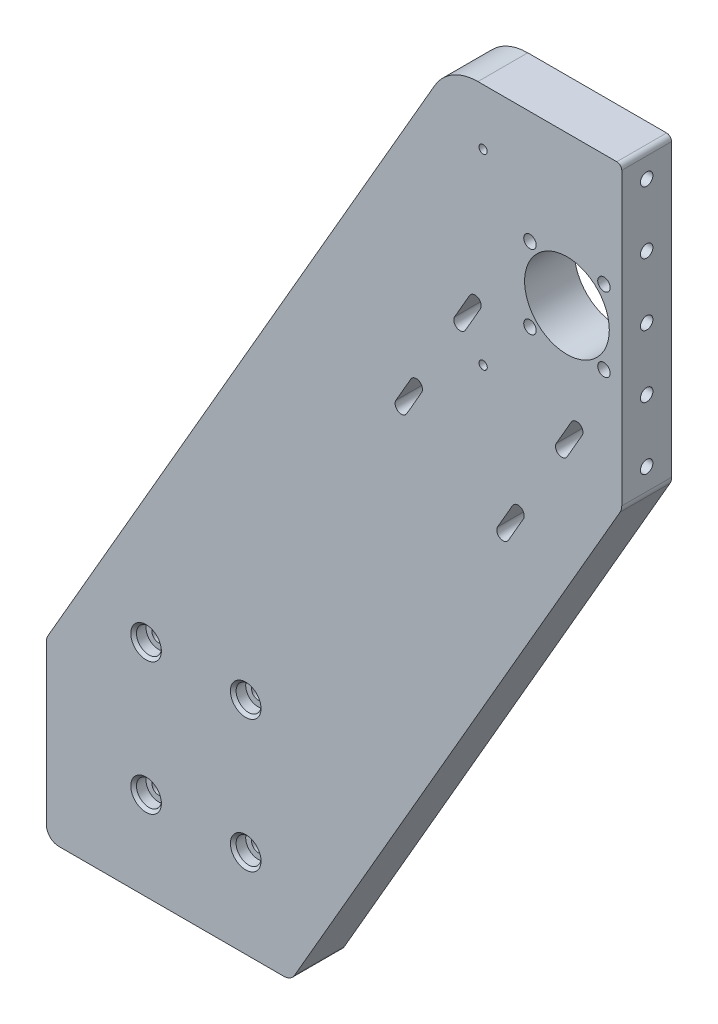
SolidWorks part; units mm, degrees
ref_plane "Piano frontale" through (0, 0, 0) normal (0, 0, 1) x (1, 0, 0)
ref_plane "Piano superiore" through (0, 0, 0) normal (0, 1, 0) x (1, 0, 0)
ref_plane "Piano destro" through (0, 0, 0) normal (1, 0, 0) x (0, 0, -1)
sketch "Schizzo1" plane through (0, 0, 0) normal (0, 0, 1) x (1, 0, 0)
  line L0 (5, 0) -> (95.2628, 0)
  line L1 (99.5929, 2.5) -> (230.2702, 228.8397)
  line L2 (230.9401, 231.3397) -> (230.9401, 348)
  line L3 (228.9401, 350) -> (173.2051, 350)
  line L4 (0, 68.6603) -> (0, 5)
  line L5 (155.8846, 340) -> (0.6699, 71.1603)
  line L9 (208.9401, 290) -> (194.0909, 304.8492) construction
  line L10 (208.9401, 290) -> (187.9401, 290) construction
  line L11 (208.9401, 290) -> (208.9401, 311) construction
  line L12 (50.1314, 0) -> (50.1314, 156.8301) construction
  circle A4 centre (208.9401, 290) radius 17
  circle A5 centre (208.9401, 290) radius 21 construction
  arc A6 (99.5929, 2.5) -> (95.2628, 0) centre (95.2628, 5) cw
  arc A7 (5, 0) -> (0, 5) centre (5, 5) cw
  arc A8 (0, 68.6603) -> (0.6699, 71.1603) centre (5, 68.6603) cw
  arc A9 (230.9401, 231.3397) -> (230.2702, 228.8397) centre (225.9401, 231.3397) cw
  arc A10 (230.9401, 348) -> (228.9401, 350) centre (228.9401, 348) ccw
  arc A11 (173.2051, 350) -> (155.8846, 340) centre (173.2051, 330) ccw
  circle A14 centre (223.7894, 304.8492) radius 2.5
  circle A15 centre (223.7894, 275.1508) radius 2.5
  circle A18 centre (194.0909, 275.1508) radius 2.5
  circle A19 centre (194.0909, 304.8492) radius 2.5
  point P27 (194.0909, 304.8492)
  point P28 (223.7894, 304.8492)
  point P29 (223.7894, 275.1508)
  point P30 (194.0909, 275.1508)
  point P31 (230.9401, 350)
  point P39 (0, 0)
  point P42 (0, 70)
  point P45 (230.9401, 230)
  point P48 (230.9401, 350)
  dimension "D6" = 60
  dimension "D9" = 34
  dimension "D11" = 45
  dimension "D14" = 5
  dimension "D15" = 5
  dimension "D17" = 42
  dimension "D12" = 2
  dimension "D1" = 120
  dimension "D2" = 120
  dimension "D3" = 70
  dimension "D4" = 350
  dimension "D5" = 120
  dimension "D10" = 22
extrude "Estrusione-Estrusione2" add sketch "Schizzo1" against normal blind 20
sketch "Sketch1" plane through (0, 0, 0) normal (0, -1, 0) x (1, 0, 0)
  line L0 (5, -10) -> (95.2628, -10) construction
  line L1 (5, -20) -> (5, 0) construction
  line L2 (95.2628, -20) -> (95.2628, 0) construction
  line L3 (50.1314, 0) -> (50.1314, -20) construction
  line L4 (5, 0) -> (95.2628, 0) construction
  line L5 (5, -20) -> (95.2628, -20) construction
  point P12 (50.1314, -10)
  point P13 (85.1314, -10)
  point P14 (15.1314, -10)
  dimension "D1" = 35
hole_wizard "M5 Tapped Hole1" positions "3DSketch1" profile "Sketch2" tap size "M5" standard "ISO"
sketch3d "3DSketch1"
  point P0 (50.1314, 0, -10)
  point P3 (85.1314, 0, -10)
  point P6 (15.1314, 0, -10)
sketch "Sketch2" plane through (50.1314, 0, -10) normal (1, 0, 0) x (0, 0, -1)
  line L0 (0, 0) -> (0, 18.6618)
  line L1 (0, 18.6618) -> (2.1, 17.4)
  line L2 (2.1, 17.4) -> (2.1, 0)
  line L5 (2.1, 0) -> (0, 0)
  line L10 (0, 18.6618) -> (-2.1, 17.4) construction
  line L11 (0, -6.35) -> (0, 107.95) construction
  dimension "Tap Drill Dia." = 4.2
  dimension "Tap Drill Depth" = 17.4
  dimension "Drill Angle" = 118
sketch "Sketch3" plane through (0, 0, 0) normal (0, 0, 1) x (1, 0, 0)
  line L0 (0, 68.6603) -> (0, 5) construction
  point P0 (40, 88.5)
  point P1 (80, 88.5)
  point P2 (80, 35.5)
  point P3 (40, 35.5)
  dimension "D1" = 40
  dimension "D2" = 53
  dimension "D3" = 40
hole_wizard "CBORE for M5 SHCS1" positions "3DSketch3" profile "Sketch5" counterbore size "M5" standard "ANSI Metric" end condition through all
sketch3d "3DSketch3"
  point P0 (80, 88.5, 0)
  point P3 (80, 35.5, 0)
  point P6 (40, 35.5, 0)
  point P9 (40, 88.5, 0)
sketch "Sketch5" plane through (80, 88.5, 0) normal (1, 0, 0) x (0, -1, 0)
  line L0 (0, 0) -> (0, 20)
  line L1 (0, 20) -> (2.65, 20)
  line L3 (2.65, 20) -> (2.65, 5)
  line L4 (5, 5) -> (2.65, 5)
  line L5 (5, 5) -> (5, 1.145)
  line L6 (5, 1.145) -> (6.145, 0)
  line L7 (6.145, 0) -> (0, 0)
  line L8 (-5, 1.145) -> (-6.145, 0) construction
  line L11 (0, -6.35) -> (0, 107.95) construction
  dimension "Thru Hole Dia." = 5.3
  dimension "Thru Hole Depth" = 20
  dimension "C'Bore Dia." = 10
  dimension "C'Bore Depth" = 5
  dimension "Near C'Sink Dia." = 12.29
  dimension "Near C'Sink Angle" = 90
sketch "Sketch7" plane through (230.9401, 0, 0) normal (1, 0, 0) x (0, 0, -1)
  point P0 (10, 340)
  point P1 (10, 315)
  point P2 (10, 290)
  point P3 (10, 265)
  point P4 (10, 240)
hole_wizard "M6 Tapped Hole1" positions "3DSketch6" profile "Sketch12" tap size "M6" standard "ISO"
sketch3d "3DSketch6"
  point P0 (230.9401, 340, -10)
  point P3 (230.9401, 315, -10)
  point P6 (230.9401, 290, -10)
  point P9 (230.9401, 265, -10)
  point P12 (230.9401, 240, -10)
sketch "Sketch12" plane through (230.9401, 340, -10) normal (0, 1, 0) x (0, 0, -1)
  line L0 (0, 0) -> (0, 20.5022)
  line L1 (0, 20.5022) -> (2.5, 19)
  line L2 (2.5, 19) -> (2.5, 0)
  line L5 (2.5, 0) -> (0, 0)
  line L10 (0, 20.5022) -> (-2.5, 19) construction
  line L11 (0, -6.35) -> (0, 107.95) construction
  dimension "Tap Drill Dia." = 5
  dimension "Tap Drill Depth" = 19
  dimension "Drill Angle" = 118
sketch "Sketch13" plane through (0, 0, 0) normal (0, 0, 1) x (1, 0, 0)
  point P0 (175.2886, 327.5068)
  point P1 (175.3131, 252.4712)
hole_wizard "M4 Tapped Hole1" positions "3DSketch10" profile "Sketch16" tap size "M4" standard "ISO" end condition through all
sketch3d "3DSketch10"
  point P0 (175.2886, 327.5068, 0)
  point P3 (175.3131, 252.4712, 0)
sketch "Sketch16" plane through (175.2886, 327.5068, 0) normal (1, 0, 0) x (0, -1, 0)
  line L0 (0, 0) -> (0, 20)
  line L1 (0, 20) -> (1.65, 20)
  line L2 (1.65, 20) -> (1.65, 0)
  line L5 (1.65, 0) -> (0, 0)
  line L11 (0, -6.35) -> (0, 107.95) construction
  dimension "Thread Major Dia." = 3.3
  dimension "Thru Tap Drill Depth" = 20
sketch "Sketch18" plane through (0, 0, 0) normal (0, 0, 1) x (1, 0, 0)
  line L0 (166.0253, 262.3194) -> (172.0253, 272.7117) construction
  line L1 (163.8602, 263.5694) -> (169.8602, 273.9617)
  line L2 (168.1903, 261.0694) -> (174.1903, 271.4617)
  line L3 (99.5929, 2.5) -> (230.2702, 228.8397) construction
  line L4 (206.8501, 238.7492) -> (212.8501, 249.1415) construction
  line L5 (204.6851, 239.9992) -> (210.6851, 250.3915)
  line L6 (209.0152, 237.4992) -> (215.0152, 247.8915)
  line L7 (183.2801, 197.9247) -> (189.2801, 208.317) construction
  line L8 (181.1151, 199.1747) -> (187.1151, 209.567)
  line L9 (185.4452, 196.6747) -> (191.4452, 207.067)
  line L10 (142.4557, 221.4947) -> (148.4557, 231.887) construction
  line L11 (140.2906, 222.7447) -> (146.2906, 233.137)
  line L12 (144.6208, 220.2447) -> (150.6208, 230.637)
  arc A0 (163.8602, 263.5694) -> (168.1903, 261.0694) centre (166.0253, 262.3194) ccw
  arc A1 (174.1903, 271.4617) -> (169.8602, 273.9617) centre (172.0253, 272.7117) ccw
  arc A2 (204.6851, 239.9992) -> (209.0152, 237.4992) centre (206.8501, 238.7492) ccw
  arc A3 (215.0152, 247.8915) -> (210.6851, 250.3915) centre (212.8501, 249.1415) ccw
  arc A4 (181.1151, 199.1747) -> (185.4452, 196.6747) centre (183.2801, 197.9247) ccw
  arc A5 (191.4452, 207.067) -> (187.1151, 209.567) centre (189.2801, 208.317) ccw
  arc A6 (140.2906, 222.7447) -> (144.6208, 220.2447) centre (142.4557, 221.4947) ccw
  arc A7 (150.6208, 230.637) -> (146.2906, 233.137) centre (148.4557, 231.887) ccw
  point P2 (169.0253, 267.5156)
  point P11 (209.8501, 243.9453)
  point P17 (186.2801, 203.1209)
  point P24 (145.4557, 226.6909)
  point P30 (145.4557, 226.6909)
  point P31 (186.2801, 203.1209)
  point P32 (209.8501, 243.9453)
  dimension "D1" = 5
  dimension "D2" = 12
extrude "Cut-Extrude2" cut sketch "Sketch18" against normal through all
